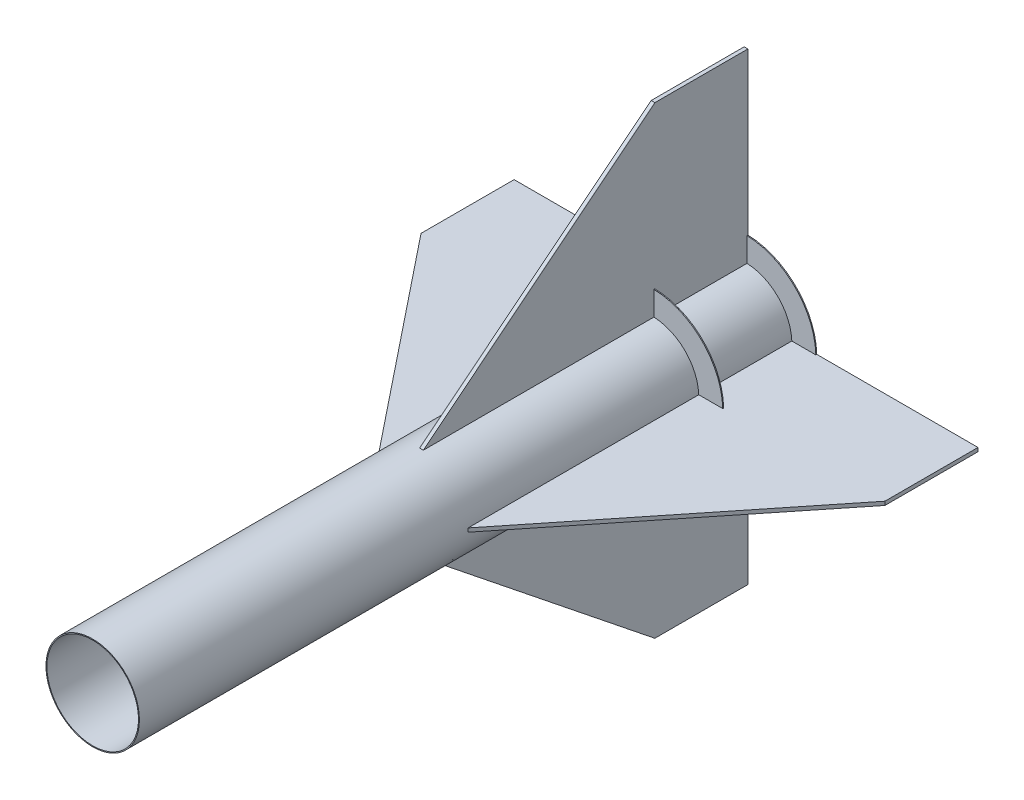
SolidWorks part; units mm, degrees
ref_plane "Front Plane" through (0, 0, 0) normal (0, 0, 1) x (1, 0, 0)
ref_plane "Top Plane" through (0, 0, 0) normal (0, 1, 0) x (1, 0, 0)
ref_plane "Right Plane" through (0, 0, 0) normal (1, 0, 0) x (0, 0, -1)
sketch "Sketch3" plane through (0, 0, 0) normal (0, 0, 1) x (1, 0, 0)
  circle A0 centre (0, 0) radius 49.2125
  circle A1 centre (0, 0) radius 50.2125
  dimension "D1" = 98.425
  dimension "D2" = 1
extrude "Boss-Extrude1" add sketch "Sketch3" along normal blind 702
sketch "Sketch4" plane through (0, 0, 0) normal (0, 0, -1) x (-1, 0, 0)
  circle A0 centre (0, 0) radius 49.2125 construction
  circle A1 centre (0, 0) radius 49.2125
  circle A2 centre (0, 0) radius 76
  dimension "D1" = 152
extrude "Boss-Extrude2" add sketch "Sketch4" against normal blind 1
ref_plane "Plane4" through (0, 0, 100) normal (0, 0, -1) x (-1, 0, 0)
sketch "Sketch5" plane through (0, 0, 100) normal (0, 0, -1) x (-1, 0, 0)
  circle A0 centre (0, 0) radius 49.2125 construction
  circle A1 centre (0, 0) radius 49.2125
  circle A2 centre (0, 0) radius 76 construction
  circle A3 centre (0, 0) radius 76
extrude "Boss-Extrude3" add sketch "Sketch5" against normal blind 1 contours A3
ref_plane "Plane5" through (0, 0, 0) normal (0, 1, 0) x (1, 0, 0)
sketch "Sketch6" plane through (0, 0, 0) normal (0, 1, 0) x (1, 0, 0)
  line L0 (-49.2125, 0) -> (-49.2125, -151.9538) construction
  line L1 (-49.2125, 0) -> (-54.566, 0) construction
  line L2 (76, 0) -> (-76, 0) construction
  line L3 (49.2125, 0) -> (-49.2125, 0) construction
  line L4 (-49.2125, 0) -> (-49.2125, -350)
  line L5 (-49.2125, 0) -> (-249.2125, 0)
  line L6 (-249.2125, 0) -> (-249.2125, -100)
  line L7 (-249.2125, -100) -> (-49.2125, -350)
  dimension "D1" = 350
  dimension "D2" = 200
  dimension "D3" = 100
extrude "Boss-Extrude4" add sketch "Sketch6" along normal blind 2 and the other way blind 2
pattern_circular "CirPattern1" count 4 over 360 about axis through (0, 0, 702) along (0, 0, -1) of "Boss-Extrude4"
